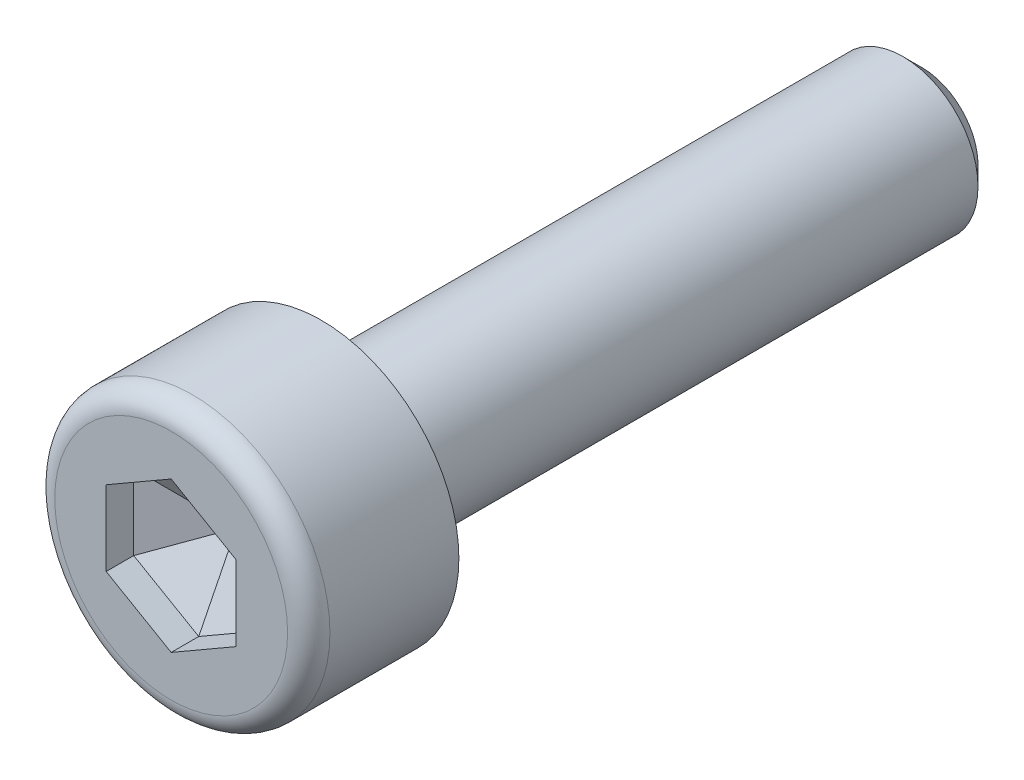
SolidWorks part; units mm, degrees
material "普通碳钢"
ref_plane "前视基准面" through (0, 0, 0) normal (0, 0, 1) x (1, 0, 0)
ref_plane "上视基准面" through (0, 0, 0) normal (0, 1, 0) x (1, 0, 0)
ref_plane "右视基准面" through (0, 0, 0) normal (1, 0, 0) x (0, 0, -1)
sketch "草图1" plane through (0, 0, 0) normal (0, 0, 1) x (1, 0, 0)
  circle A0 centre (0, 0) radius 2.75
  dimension "dk" = 5.5
extrude "凸台-拉伸1" add sketch "草图1" along normal blind 3
ref_axis "基准轴1" through (0, 0, 3) along (0, 0, -1)
sketch "草图2" plane through (0, 0, 3) normal (0, 0, 1) x (1, 0, 0)
  line L1 (1.3, 0.7506) -> (0, 1.5011)
  line L2 (0, 1.5011) -> (-1.3, 0.7506)
  line L3 (-1.3, 0.7506) -> (-1.3, -0.7506)
  line L4 (-1.3, -0.7506) -> (0, -1.5011)
  line L5 (0, -1.5011) -> (1.3, -0.7506)
  line L6 (1.3, -0.7506) -> (1.3, 0.7506)
  circle A0 centre (0, 0) radius 1.3 construction
  dimension "s" = 2.6
extrude "切除-拉伸1" cut sketch "草图2" against normal blind 1.3
sketch "草图3" plane through (0, 0, 0) normal (0, 0, -1) x (-1, 0, 0)
  circle A0 centre (0, 0) radius 1.5
  dimension "d" = 3
extrude "凸台-拉伸2" add sketch "草图3" along normal blind 12
cosmetic thread "装饰螺纹线1" parameters "b"=4.9, "D2"=1.221
chamfer "倒角1" distance 0.375 angle 45 1 edges at (-1.5, 0, -12)
fillet "圆角1" radius 0.4231 1 edges at (2.75, 0, 3)
chamfer "倒角2" distance 0.7493 angle 60 6 edges at (-1.3, 0, 1.7) (-0.65, 1.1258, 1.7) (0.65, 1.1258, 1.7) (1.3, 0, 1.7) (-0.65, -1.1258, 1.7) (0.65, -1.1258, 1.7) first distance on face at (-1.3, 0, 2.35) first distance on face at (-0.65, 1.1258, 2.35) first distance on face at (0.65, 1.1258, 2.35) first distance on face at (1.3, 0, 2.35) first distance on face at (-0.65, -1.1258, 2.35) first distance on face at (0.65, -1.1258, 2.35)
fillet "圆角2" radius 0.1 1 edges at (1.5, 0, 0)
ref_plane "基准面1" through (0, 0, 0) normal (0, 0, -1) x (-1, 0, 0)
equation "\"D1@倒角2\" = \"s@草图2\" / 3.47"
equation "\"D1@圆角1\"= \"dk@草图1\" / 13"
equation "\"D1@倒角1\"= \"d@草图3\" / 8"
equation "\"D1@圆角2\"= \"d@草图3\" / \"d@草图3\" * 0.1"
